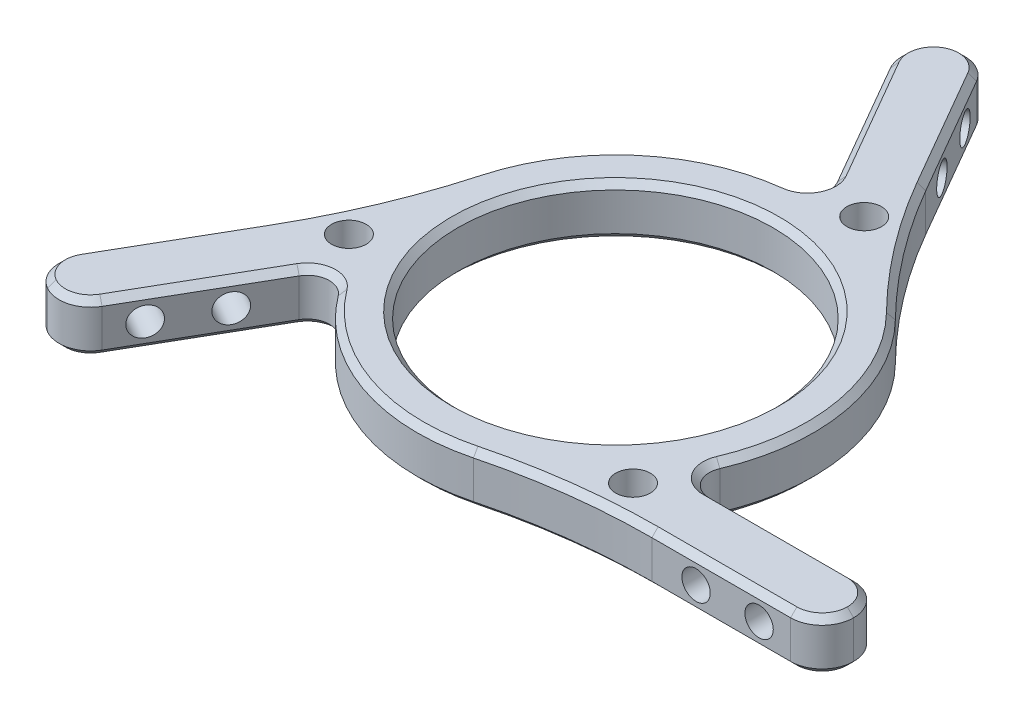
SolidWorks part; units mm, degrees
ref_plane "Front Plane" through (0, 0, 0) normal (0, 0, 1) x (1, 0, 0)
ref_plane "Top Plane" through (0, 0, 0) normal (0, 1, 0) x (1, 0, 0)
ref_plane "Right Plane" through (0, 0, 0) normal (1, 0, 0) x (0, 0, -1)
sketch "Sketch1" plane through (0, 0, 0) normal (0, 1, 0) x (1, 0, 0)
  line L0 (0, 0) -> (77.2289, 0) construction
  line L1 (0, 0) -> (-45.1019, 78.1188) construction
  line L2 (0, 0) -> (-40.4778, -70.1095) construction
  line L3 (60, -17.2) -> (60, -27.2)
  line L4 (60, -27.2) -> (-15.7039, -27.2)
  line L5 (60, -17.2) -> (-9.9304, -17.2)
  line L6 (-44.8956, -43.3615) -> (-9.9304, 17.2)
  line L7 (-53.5559, -38.3615) -> (-15.7039, 27.2)
  line L8 (-44.8956, -43.3615) -> (-53.5559, -38.3615)
  line L9 (-15.1044, 60.5615) -> (19.8608, 0)
  line L10 (-6.4441, 65.5615) -> (31.4079, 0)
  line L11 (-15.1044, 60.5615) -> (-6.4441, 65.5615)
  circle A0 centre (0, 0) radius 31.4079
  point P20 (0, 0)
  dimension "D1" = 120
  dimension "D2" = 240
  dimension "D3" = 60
  dimension "D5" = 17.2
  dimension "D6" = 10
  dimension "D4" = 3
extrude "Boss-Extrude1" add sketch "Sketch1" along normal blind 8 contours A0 L10 L11 L9 | A0 L4 L3 L5 | A0 L7 L8 L6 | A0 region at (40.7936, 0, 22.4254) region at (-0.9758, 0, -46.541) region at (-39.8178, 0, 24.1155)
sketch "Sketch2" plane through (0, 0, 17.2) normal (0, 0, -1) x (-1, 0, 0)
  line L0 (-50, 4) -> (-40, 4) construction
  line L1 (-60, 8) -> (-60, 0) construction
  circle A0 centre (-50, 4) radius 2.25
  circle A1 centre (-40, 4) radius 2.25
  point P4 (-45, 4)
  point P8 (-60, 4)
  dimension "D1" = 4.5
  dimension "D2" = 10
  dimension "D3" = 45
extrude "Cut-Extrude1" cut sketch "Sketch2" against normal through all
sketch "Sketch4" plane through (0, 8, 0) normal (0, 1, 0) x (1, 0, 0)
  line L0 (60, -17.2) -> (60, -27.2) construction
  line L1 (0, 0) -> (25, -22.2) construction
  line L2 (0, 0) -> (48.4694, 0) construction
  line L3 (0, 0) -> (6.7258, 32.7506) construction
  line L4 (0, 0) -> (0, 67.7264) construction
  circle A0 centre (25, -22.2) radius 2.75
  circle A1 centre (0, 0) radius 25
  circle A2 centre (-31.7258, -10.5506) radius 2.75
  circle A3 centre (6.7258, 32.7506) radius 2.75
  point P10 (60, -22.2)
  point P14 (0, 0)
  dimension "D1" = 5.5
  dimension "D2" = 50
  dimension "D3" = 25
  dimension "D5" = 11.605
  dimension "D4" = 3
extrude "Cut-Extrude2" cut sketch "Sketch4" along direction (0, 1, 0) on the side against the normal through all contours A1 | A0 | A2 | A3 region at (0, 8, 0)
fillet "Fillet1" radius 5 6 edges at (-6.4441, 4, -65.5615) (-15.1044, 4, -60.5615) (-53.5559, 4, 38.3615) (-44.8956, 4, 43.3615) (60, 4, 17.2) (60, 4, 27.2)
fillet "Fillet2" radius 100 3 edges at (15.7039, 4, -27.2) (-31.4079, 4, 0) (15.7039, 4, 27.2)
fillet "Fillet3" radius 3.5 3 edges at (1.7559, 4, -31.3587) (-28.0354, 4, 14.1587) (26.2795, 4, 17.2)
sketch "Sketch5" plane through (-14.8956, 0, -8.6) normal (0.866, 0, 0.5) x (0.5, 0, -0.866)
  line L0 (-50, 4) -> (-40, 4) construction
  circle A0 centre (-50, 4) radius 2.25
  circle A1 centre (-40, 4) radius 2.25
  point P4 (-45, 4)
  dimension "D1" = 4.5
  dimension "D2" = 10
  dimension "D3" = 45
extrude "Cut-Extrude3" cut sketch "Sketch5" against normal through all
sketch "Sketch6" plane through (14.8956, 0, -8.6) normal (-0.866, 0, 0.5) x (0.5, 0, 0.866)
  line L0 (-60, 4) -> (-52.23, 4) construction
  line L1 (-60, 0) -> (-60, 8) construction
  line L2 (-50, 4) -> (-40, 4) construction
  circle A0 centre (-50, 4) radius 2.25
  circle A1 centre (-40, 4) radius 2.25
  point P8 (-45, 4)
  dimension "D1" = 4.5
  dimension "D2" = 45
  dimension "D3" = 10
extrude "Cut-Extrude4" cut sketch "Sketch6" against normal through all
chamfer "Chamfer1" distance 1 angle 45 44 edges at (-13.1039, 0, -60.0255) (-6.9801, 0, -63.561) (-6.8811, 0, -46.3185) (1.559, 0, -51.6998) (-1.0582, 0, -33.091) (14.0848, 0, -31.6119) (-20.4874, 0, -23.8059) (30.8602, 0, -5.8397) (-34.4191, 0, 3.6081) (29.1867, 0, 15.629) (-45.5528, 0, 24.4998) (43.5536, 0, 17.2) (-51.5554, 0, 37.8255) (58.5355, 0, 18.6645) (-45.4317, 0, 41.361) (58.5355, 0, 25.7355) (-36.6724, 0, 29.1185) (43.9938, 0, 27.2) (-28.1285, 0, 17.4619) (20.3343, 0, 28.0038) (-10.3728, 0, 29.6456) (58.5355, 8, 18.6645) (58.5355, 8, 25.7355) (43.5536, 8, 17.2) (43.9938, 8, 27.2) (29.1867, 8, 15.629) (20.3343, 8, 28.0038) (30.8602, 8, -5.8397) (-10.3728, 8, 29.6456) (14.0848, 8, -31.6119) (-28.1285, 8, 17.4619) (1.559, 8, -51.6998) (-36.6724, 8, 29.1185) (-6.9801, 8, -63.561) (-45.4317, 8, 41.361) (-13.1039, 8, -60.0255) (-51.5554, 8, 37.8255) (-6.8811, 8, -46.3185) (-45.5528, 8, 24.4998) (-1.0582, 8, -33.091) (-34.4191, 8, 3.6081) (-20.4874, 8, -23.8059) (0, 0, 25) (0, 8, 25)
sketch "Sketch7" plane through (0, 0, 0) normal (0, 1, 0) x (1, 0, 0)
  line L0 (0, 0) -> (71.2229, 0)
  line L1 (32.1071, -17.2) -> (55, -17.2) construction
  line L2 (32.1071, -17.2) -> (55, -17.2)
  line L3 (0, 0) -> (-27.7255, -48.022)
  line L4 (0, 0) -> (-27.1961, 47.1051)
  dimension "D1" = 17.2
  dimension "D2" = 120
  dimension "D3" = 240
equation "\"mounting hole\"= 5.5mm"
equation "\"servo holes\"= 4.5mm"
equation "\"mounting hole dist from center\"= 25mm"
equation "\"D3@Sketch4\"=\"mounting hole dist from center\""
equation "\"D1@Sketch4\"=\"mounting hole\""
equation "\"mounting sketch rotation\"= 11.60507646deg"
equation "\"D1@Sketch2\"=\"servo holes\""
equation "\"servo hole dist from center\"= 45mm"
equation "\"D3@Sketch2\"=\"servo hole dist from center\""
equation "\"D1@Sketch5\"=\"servo holes\""
equation "\"D3@Sketch5\"=\"servo hole dist from center\""
equation "\"D1@Sketch6\"=\"servo holes\""
equation "\"D2@Sketch6\"=\"servo hole dist from center\""
